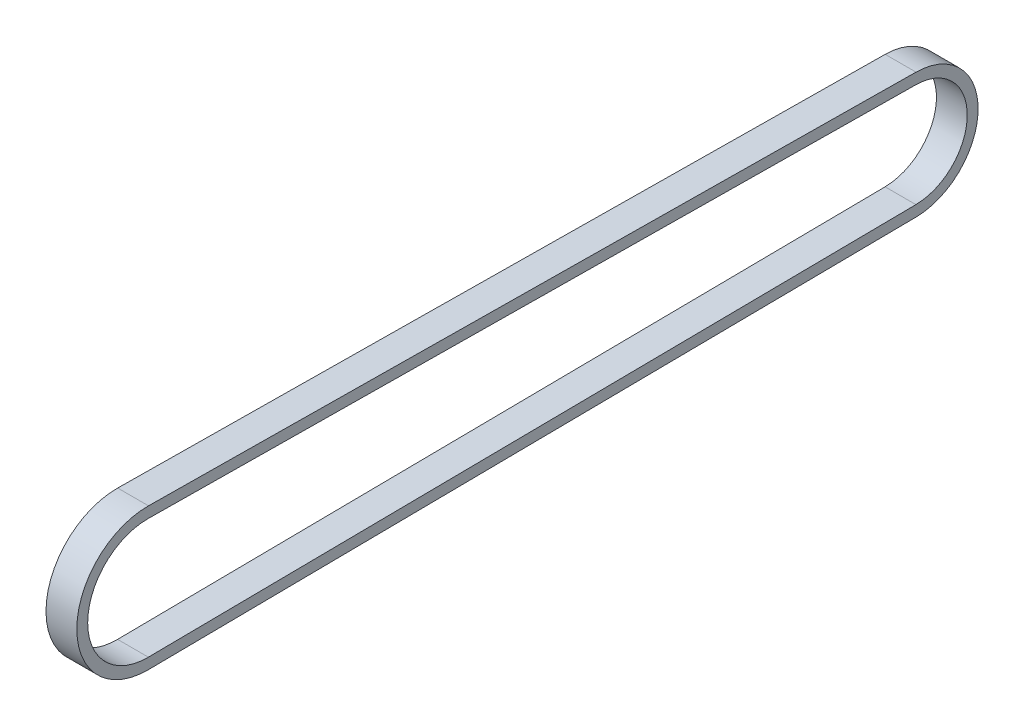
SolidWorks part; units mm, degrees
ref_plane "Front Plane" through (0, 0, 0) normal (0, 0, 1) x (1, 0, 0)
ref_plane "Top Plane" through (0, 0, 0) normal (0, 1, 0) x (1, 0, 0)
ref_plane "Right Plane" through (0, 0, 0) normal (1, 0, 0) x (0, 0, -1)
other "Bounding Box"
ref_plane "Default Plane" through (-8.9266, -12.7485, 0) normal (-0.1736, 0.9848, 0) x (0.9848, 0.1736, 0)
sketch "Sketch1" plane through (0, 0, 0) normal (1, 0, 0) x (0, 0, -1)
  line L0 (0, 0) -> (224.2363, 0) construction
  line L1 (0.1867, 17.5479) -> (224.3976, 15.1629)
  line L2 (0.1867, -17.5479) -> (224.3976, -15.1629)
  line L3 (0.2204, 20.7227) -> (224.4313, 18.3378)
  line L4 (0.2204, -20.7227) -> (224.4313, -18.3378)
  line L5 (-17.5489, 0) -> (-20.7239, 0) construction
  line L6 (239.4001, 0) -> (242.5751, 0) construction
  arc A0 (0.1867, 17.5479) -> (0.1867, -17.5479) centre (0, 0) ccw
  arc A1 (224.3976, -15.1629) -> (224.3976, 15.1629) centre (224.2363, 0) ccw
  arc A2 (0.2204, 20.7227) -> (0.2204, -20.7227) centre (0, 0) ccw
  arc A3 (224.4313, -18.3378) -> (224.4313, 18.3378) centre (224.2363, 0) ccw
  dimension "D2" = 3.175
  dimension "D3" = 15.1638
  dimension "D4" = 35.0977
  dimension "D1" = 224.2363
extrude "Boss-Extrude1" add sketch "Sketch1" along normal mid plane 9
